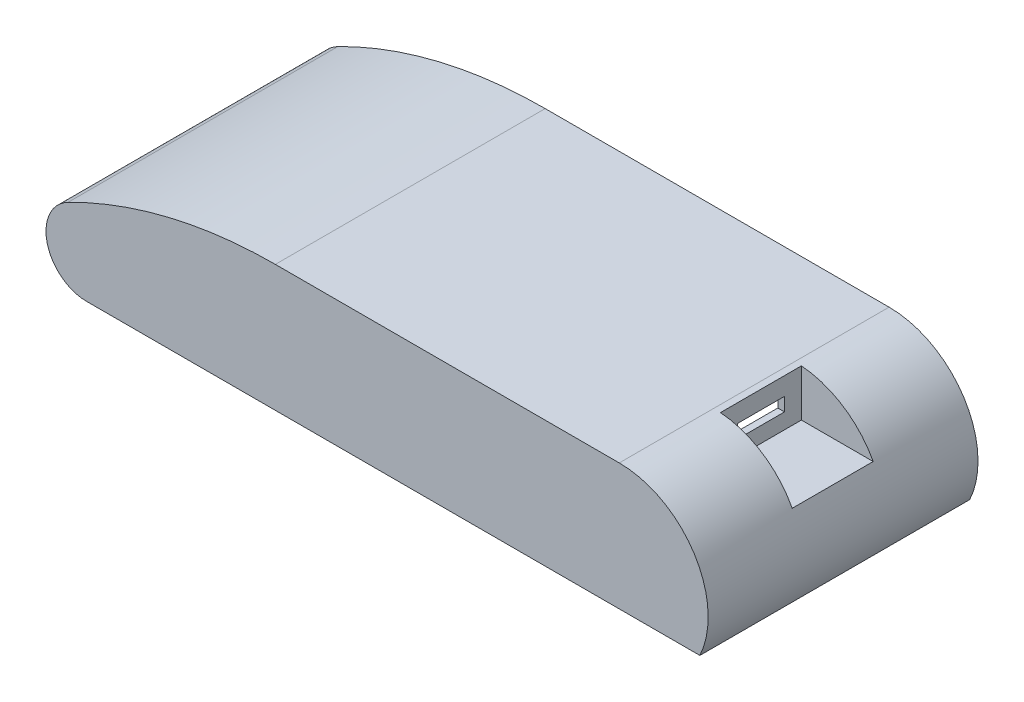
SolidWorks part; units mm, degrees
ref_plane "Front Plane" through (0, 0, 0) normal (0, 0, 1) x (1, 0, 0)
ref_plane "Top Plane" through (0, 0, 0) normal (0, 1, 0) x (1, 0, 0)
ref_plane "Right Plane" through (0, 0, 0) normal (1, 0, 0) x (0, 0, -1)
sketch "Sketch1" plane through (0, 0, 0) normal (0, 0, 1) x (1, 0, 0)
  line L0 (104.9445, -38.2227) -> (104.9445, -39.2227)
  line L1 (14.6716, -39.2227) -> (14.6716, -38.2227)
  line L2 (14.6716, -38.2227) -> (-20.7139, -38.2227) construction
  line L7 (93.6516, -21.4794) -> (42.6716, -21.4794)
  line L8 (105.6, -39.2227) -> (104.9445, -39.2227)
  line L9 (93.6516, -20.4794) -> (42.6716, -20.4794)
  line L17 (105.6, -39.2227) -> (14.6716, -39.2227) construction
  line L19 (104.9445, -38.2227) -> (14.6716, -38.2227) construction
  arc A0 (93.6516, -21.4794) -> (104.9445, -38.2227) centre (93.6516, -33.6595) cw
  arc A1 (42.6716, -21.4794) -> (12.3953, -28.7709) centre (42.6716, -87.9829) ccw
  arc A2 (12.3953, -28.7709) -> (14.6716, -38.2227) centre (14.6716, -33.2227) ccw
  arc A3 (93.6516, -20.4794) -> (105.6, -39.2227) centre (93.6516, -33.6595) cw
  arc A4 (11.9401, -27.8805) -> (14.6716, -39.2227) centre (14.6716, -33.2227) ccw
  arc A5 (42.6716, -20.4794) -> (11.9401, -27.8805) centre (42.6716, -87.9829) ccw
  point P6 (0, 0)
  dimension "D9" = 5
  dimension "D2" = 1
  dimension "D3" = 50.98
  dimension "D4" = 17.7433
  dimension "D5" = 11.2929
  dimension "D8" = 28
  dimension "D1" = 1
extrude "Boss-Extrude1" add sketch "Sketch1" along normal blind 38 contours L9 A5 A4 A2 A1 L7 A0 L8 A3 region at (104.578, -26.2899, 0)
sketch "Sketch2" plane through (0, 0, 0) normal (0, 0, -1) x (-1, 0, 0)
  line L0 (-104.9445, -39.2227) -> (-14.6716, -39.2227)
  line L6 (-104.9445, -39.2227) -> (-104.9445, -38.2227)
  line L8 (-42.6716, -20.4794) -> (-93.6516, -20.4794)
  line L9 (-105.6, -39.2227) -> (-104.9445, -39.2227)
  line L10 (-14.6716, -38.2227) -> (-14.6716, -39.2227)
  line L12 (-93.6516, -21.4794) -> (-42.6716, -21.4794)
  line L16 (-42.6716, -20.4794) -> (-93.6516, -20.4794)
  line L17 (-105.6, -39.2227) -> (-104.9445, -39.2227)
  arc A6 (-93.6516, -20.4794) -> (-105.6, -39.2227) centre (-93.6516, -33.6595) ccw
  arc A7 (-93.6516, -21.4794) -> (-104.9445, -38.2227) centre (-93.6516, -33.6595) ccw
  arc A8 (-12.3953, -28.7709) -> (-42.6716, -21.4794) centre (-42.6716, -87.9829) ccw
  arc A9 (-14.6716, -38.2227) -> (-12.3953, -28.7709) centre (-14.6716, -33.2227) ccw
  arc A10 (-14.6716, -39.2227) -> (-11.9401, -27.8805) centre (-14.6716, -33.2227) ccw
  arc A11 (-11.9401, -27.8805) -> (-42.6716, -20.4794) centre (-42.6716, -87.9829) ccw
  arc A12 (-93.6516, -20.4794) -> (-105.6, -39.2227) centre (-93.6516, -33.6595) ccw
  arc A16 (-14.6716, -39.2227) -> (-11.9401, -27.8805) centre (-14.6716, -33.2227) ccw
  arc A17 (-11.9401, -27.8805) -> (-42.6716, -20.4794) centre (-42.6716, -87.9829) ccw
  point P2 (10.0223, -4.3224)
  dimension "D1" = 0
extrude "Boss-Extrude2" add sketch "Sketch2" along normal blind 1
ref_plane "Plane1" through (0, 0, 19) normal (0, 0, 1) x (1, 0, 0)
mirror "Mirror1" about plane through (0, 0, 19) normal (0, 0, 1) of "Boss-Extrude2"
sketch "Sketch5" plane through (0, -21.4794, 0) normal (0, -1, 0) x (1, 0, 0)
  line L0 (42.6716, 38) -> (42.6716, 0) construction
  line L1 (45.3016, 27.89) -> (45.3016, 10.11) construction
  circle A0 centre (45.3016, 27.89) radius 1.5
  circle A1 centre (45.3016, 10.11) radius 1.5
  circle A2 centre (91.0216, 27.89) radius 1.5
  circle A3 centre (91.0216, 10.11) radius 1.5
  point P6 (42.6716, 19)
  point P7 (45.3016, 19)
  dimension "D3" = 3
  dimension "D1" = 2.63
  dimension "D2" = 17.78
  dimension "D4" = 2
extrude "Boss-Extrude4" add sketch "Sketch5" along normal blind 2
sketch "Sketch6" plane through (0, -39.2227, 0) normal (0, -1, 0) x (1, 0, 0)
  line L0 (14.6716, 38) -> (14.6716, 0) construction
  line L2 (14.6716, 31.5) -> (10.6716, 31.5)
  line L3 (14.6716, 31.5) -> (14.6716, 6.5)
  line L4 (14.6716, 6.5) -> (10.6716, 6.5)
  line L5 (10.6716, 31.5) -> (10.6716, 6.5)
  point P6 (14.6716, 19)
  point P7 (10.6716, 19)
  dimension "D1" = 25
  dimension "D2" = 4
extrude "Cut-Extrude1" cut sketch "Sketch6" against normal up to next
ref_plane "Plane2" through (106.8317, 0, 0) normal (1, 0, 0) x (0, 0, -1)
sketch "Sketch7" plane through (106.8317, 0, 0) normal (1, 0, 0) x (0, 0, -1)
  line L0 (-39, -20.4794) -> (1, -20.4794) construction
  line L1 (-25, -20.4794) -> (-13, -20.4794)
  line L2 (-25, -20.4794) -> (-25, -27.4794)
  line L3 (-25, -27.4794) -> (-13, -27.4794)
  line L4 (-13, -20.4794) -> (-13, -27.4794)
  point P6 (-19, -20.4794)
  point P7 (-19, -20.4794)
  dimension "D1" = 12
  dimension "D2" = 7
extrude "Cut-Extrude2" cut sketch "Sketch7" against normal up to vertex (13.18 mm away) up to point (93.6516, -20.4794, -1)
sketch "Sketch8" plane through (93.6516, 0, 0) normal (1, 0, 0) x (0, 0, -1)
  line L0 (-13, -20.4794) -> (-13, -27.4794) construction
  line L1 (-25, -27.4794) -> (-25, -20.4794) construction
  line L2 (-25, -27.4794) -> (-13, -27.4794) construction
  line L3 (-13, -20.4794) -> (-13, -27.4794) construction
  line L4 (-25, -27.4794) -> (-25, -20.4794) construction
  line L5 (-25, -27.4794) -> (-13, -27.4794) construction
  line L6 (-12, -20.4794) -> (-12, -28.4794)
  line L7 (-26, -28.4794) -> (-12, -28.4794)
  line L8 (-26, -28.4794) -> (-26, -20.4794)
  line L9 (-26, -20.4794) -> (-12, -20.4794)
  line L11 (-22.5, -23.1794) -> (-15.5, -23.1794)
  line L12 (-22.5, -23.1794) -> (-22.5, -25.1794)
  line L13 (-22.5, -25.1794) -> (-15.5, -25.1794)
  line L14 (-15.5, -23.1794) -> (-15.5, -25.1794)
  point P12 (-19, -23.1794)
  point P13 (-19, -20.4794)
  dimension "D2" = 7
  dimension "D3" = 2
  dimension "D4" = 2.7
  dimension "D1" = 1
extrude "Boss-Extrude5" add sketch "Sketch8" along normal blind 1
sketch "Sketch9" plane through (0, 0, 26) normal (0, 0, 1) x (1, 0, 0)
  line L2 (94.6516, -20.5174) -> (94.6516, -20.4794)
  line L3 (94.6516, -20.4794) -> (93.6516, -20.4794)
  line L4 (94.6516, -20.5174) -> (94.6516, -20.4794)
  line L5 (94.6516, -20.4794) -> (93.6516, -20.4794)
  arc A1 (94.6516, -20.5174) -> (93.6516, -20.4794) centre (93.6516, -33.6595) ccw
  arc A2 (94.6516, -20.5174) -> (93.6516, -20.4794) centre (93.6516, -33.6595) ccw
  dimension "D1" = 0
extrude "Cut-Extrude3" cut sketch "Sketch9" against normal up to next
sketch "Sketch10" plane through (94.6516, 0, 0) normal (1, 0, 0) x (0, 0, -1)
  line L0 (-26, -21.5205) -> (-26, -28.4794) construction
  line L1 (-26, -28.4794) -> (-12, -28.4794) construction
  line L2 (-12, -28.4794) -> (-12, -21.5205) construction
  line L3 (-26, -21.5205) -> (-26, -28.4794)
  line L4 (-26, -28.4794) -> (-12, -28.4794)
  line L5 (-12, -28.4794) -> (-12, -21.5205)
  line L6 (-25, -21.5205) -> (-25, -27.4794)
  line L7 (-25, -27.4794) -> (-13, -27.4794)
  line L8 (-13, -27.4794) -> (-13, -21.5205)
  line L9 (-26, -21.5205) -> (-25, -21.5205)
  line L10 (-12, -21.5205) -> (-13, -21.5205)
  dimension "D1" = 1
extrude "Boss-Extrude6" add sketch "Sketch10" along normal up to next
